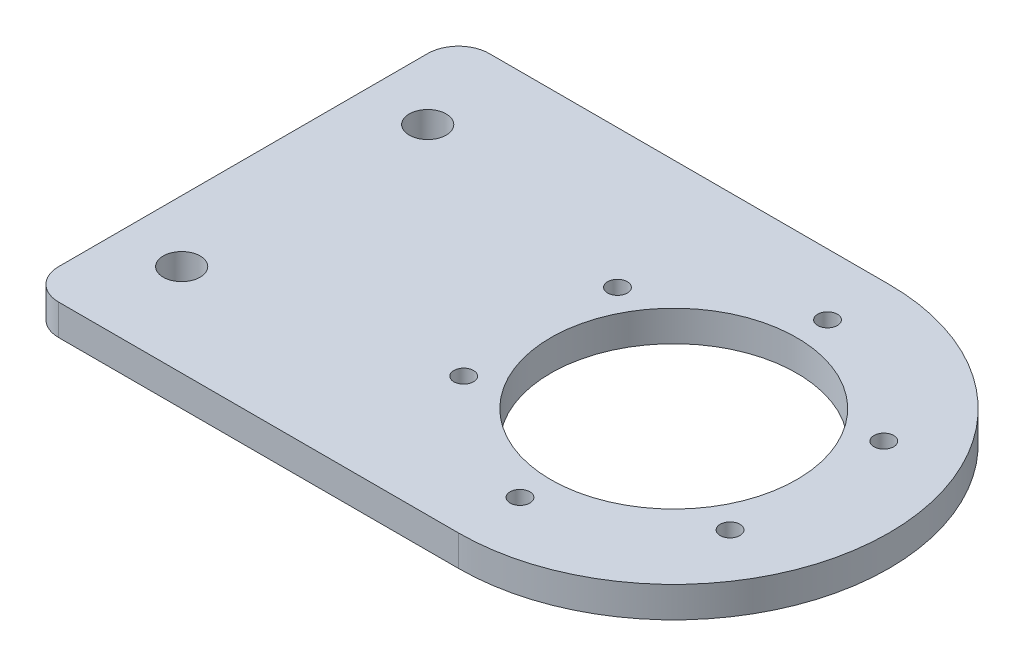
SolidWorks part; units mm, degrees
ref_plane "Front Plane" through (0, 0, 0) normal (0, 0, 1) x (1, 0, 0)
ref_plane "Top Plane" through (0, 0, 0) normal (0, 1, 0) x (1, 0, 0)
ref_plane "Right Plane" through (0, 0, 0) normal (1, 0, 0) x (0, 0, -1)
sketch "Sketch1" plane through (0, 0, 0) normal (0, 1, 0) x (1, 0, 0)
  line L0 (-70, 35) -> (0, 35)
  line L1 (0, -35) -> (-70, -35)
  line L2 (-70, -35) -> (-70, 35)
  line L3 (-60, 20) -> (-60, -20) construction
  line L4 (-103.0809, 0) -> (63.3859, 0) construction
  circle A0 centre (0, 0) radius 25 construction
  circle A1 centre (0, 25) radius 1.6
  arc A2 (0, 35) -> (0, -35) centre (0, 0) cw
  circle A3 centre (21.6506, 12.5) radius 1.6
  circle A4 centre (21.6506, -12.5) radius 1.6
  circle A5 centre (0, -25) radius 1.6
  circle A6 centre (-21.6506, -12.5) radius 1.6
  circle A7 centre (-21.6506, 12.5) radius 1.6
  circle A8 centre (0, 0) radius 20
  circle A9 centre (-60, 20) radius 3
  circle A10 centre (-60, -20) radius 3
  point P23 (0, 0)
  point P28 (-60, 0)
  dimension "D1" = 3.2
  dimension "D2" = 50
  dimension "D6" = 40
  dimension "D8" = 6
  dimension "D3" = 70
  dimension "D4" = 70
  dimension "D7" = 40
  dimension "D9" = 10
  dimension "D5" = 6
extrude "Boss-Extrude1" add sketch "Sketch1" along normal blind 5
fillet "Fillet1" radius 5 2 edges at (-70, 2.5, -35) (-70, 2.5, 35)
sketch "Sketch4" plane through (0, 0, 0) normal (0, -1, 0) x (1, 0, 0)
  circle A0 centre (0, 0) radius 25 construction
  circle A1 centre (0, 25) radius 3.25
  circle A2 centre (21.6506, 12.5) radius 3.25
  circle A3 centre (21.6506, -12.5) radius 3.25
  circle A4 centre (0, -25) radius 3.25
  circle A5 centre (-21.6506, -12.5) radius 3.25
  circle A6 centre (-21.6506, 12.5) radius 3.25
  point P18 (0, 0)
  dimension "D1" = 6.5
  dimension "D2" = 6
extrude "Cut-Extrude2" cut sketch "Sketch4" against normal blind 1.5
